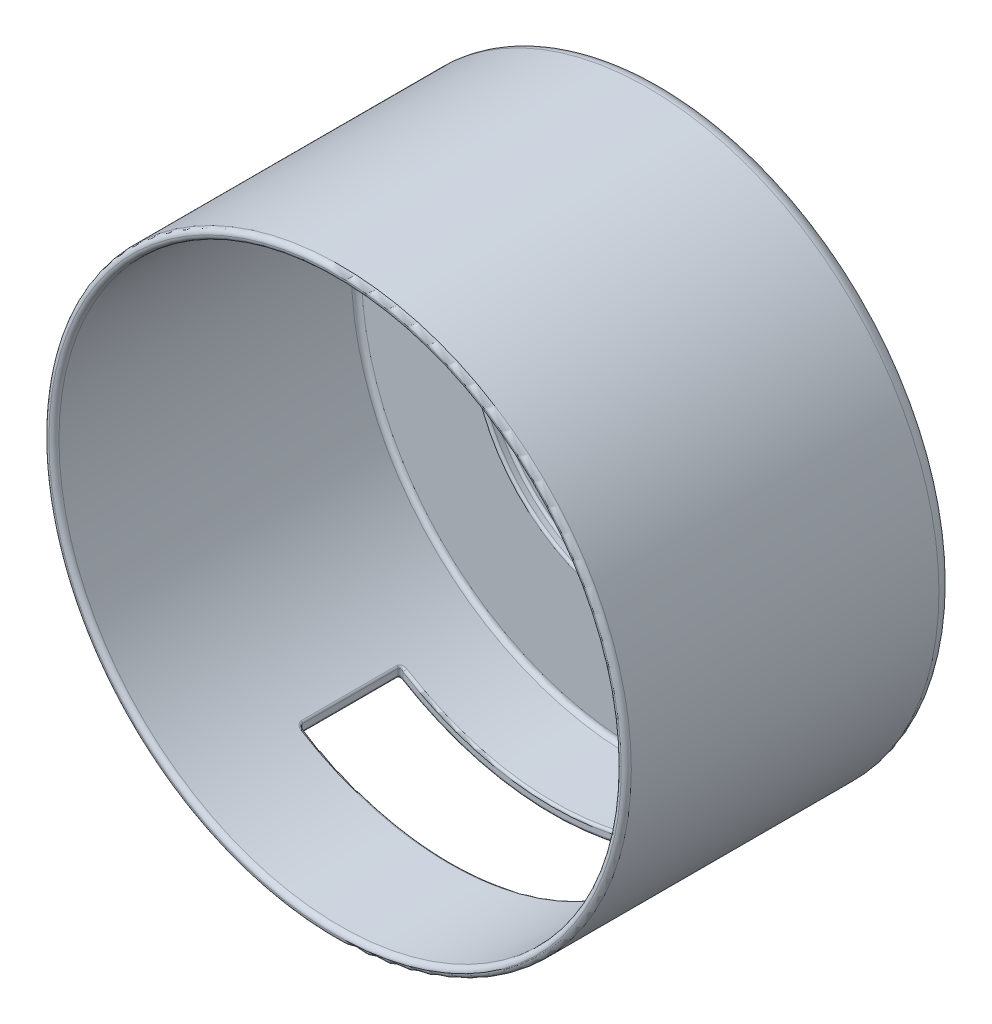
SolidWorks part; units mm, degrees
material "Custom PLA"
ref_plane "Front Plane" through (0, 0, 0) normal (0, 0, 1) x (1, 0, 0)
ref_plane "Top Plane" through (0, 0, 0) normal (0, 1, 0) x (1, 0, 0)
ref_plane "Right Plane" through (0, 0, 0) normal (1, 0, 0) x (0, 0, -1)
sketch "Sketch3" plane through (0, 0, 0) normal (0, 0, 1) x (1, 0, 0)
  circle A0 centre (0, 0) radius 57.75
  dimension "D1" = 115.5
extrude "Boss-Extrude4" add sketch "Sketch3" along normal blind 65
sketch "Sketch4" plane through (0, 0, 65) normal (0, 0, 1) x (1, 0, 0)
  circle A0 centre (0, 0) radius 55.75
  dimension "D1" = 111.5
extrude "Cut-Extrude2" cut sketch "Sketch4" against normal blind 60
sketch "Sketch5" plane through (0, 0, 0) normal (0, 0, -1) x (-1, 0, 0)
  circle A0 centre (0, 0) radius 27.5
  dimension "D1" = 55
extrude "Boss-Extrude6" add sketch "Sketch5" along normal blind 5 contours A0
sketch "Sketch10" plane through (0, 0, -5) normal (0, 0, -1) x (-1, 0, 0)
  circle A0 centre (0, 0) radius 20
  dimension "D1" = 40
extrude "Cut-Extrude5" cut sketch "Sketch10" against normal blind 40
sketch "Sketch11" plane through (0, 0, 5) normal (0, 0, -1) x (-1, 0, 0)
  circle A0 centre (0, 0) radius 23 construction
  circle A1 centre (0, 23) radius 1.55
  dimension "D1" = 46
  dimension "D2" = 3.1
extrude "Cut-Extrude6" cut sketch "Sketch11" along normal up to next
pattern_circular "CirPattern2" count 8 over 360 about axis through (0, 0, -5) along (0, 0, -1) of "Cut-Extrude6"
sketch "Sketch12" plane through (0, 0, 5) normal (0, 0, 1) x (1, 0, 0)
  circle A0 centre (0, 0) radius 32.5
  dimension "D1" = 65
extrude "Cut-Extrude7" cut sketch "Sketch12" against normal blind 2
sketch "Sketch13" plane through (0, 0, 3) normal (0, 0, 1) x (1, 0, 0)
  line L0 (0, 0) -> (0, 32.5) construction
  circle A0 centre (0, 0) radius 22.5 construction
  circle A1 centre (0, 0) radius 32.5 construction
  circle A2 centre (0, 23) radius 2.875
  dimension "D1" = 45
  dimension "D2" = 5.75
extrude "Cut-Extrude8" cut sketch "Sketch13" against normal blind 6
pattern_circular "CirPattern3" count 8 over 360 about axis through (0, 0, 5) along (0, 0, 1) of "Cut-Extrude8"
fillet "Fillet1" radius 1 3 edges at (57.75, 0, 65) (55.75, 0, 65) (55.75, 0, 5)
fillet "Fillet2" radius 3 1 edges at (57.75, 0, 0)
fillet "Fillet3" radius 0.5 2 edges at (32.5, 0, 5) (32.5, 0, 3)
fillet "Fillet4" radius 0.5 2 edges at (20, 0, 3) (-20, 0, -5)
fillet "Fillet5" radius 1 2 edges at (-27.5, 0, 0) (-27.5, 0, -5)
sketch "Sketch14" plane through (0, 0, 5) normal (0, 0, 1) x (1, 0, 0)
  line L0 (0, 62.9632) -> (0, -75.9722) construction
  circle A0 centre (0, 0) radius 42.5 construction
  circle A1 centre (0, 42.5) radius 1.8
  dimension "D1" = 85
  dimension "D2" = 3.6
extrude "Cut-Extrude9" [suppressed] cut sketch "Sketch14" against normal up to next
pattern_circular "CirPattern4" [suppressed] count 8 over 360 of bodies 117
sketch "Sketch15" [suppressed] plane through (0, 0, 0) normal (0, 0, -1) x (-1, 0, 0)
  line L0 (0, 63.4836) -> (0, -76.7527) construction
  circle A0 centre (0, 0) radius 42.5 construction
  circle A1 centre (0, 42.5) radius 3.5
  dimension "D1" = 85
  dimension "D2" = 7
extrude "Cut-Extrude10" [suppressed] cut sketch "Sketch15" against normal blind 2
pattern_circular "CirPattern5" [suppressed] count 8 over 360 of bodies 119
ref_plane "Plane1" through (0, -57.75, 0) normal (0, -1, 0) x (-1, 0, 0)
sketch "Sketch16" plane through (0, -57.75, 0) normal (0, 1, 0) x (1, 0, 0)
  line L0 (0, 13.0017) -> (0, -82.356) construction
  line L1 (56.75, -65) -> (-56.75, -65) construction
  line L2 (-30, -42) -> (30, -42)
  line L3 (-30, -42) -> (-30, -22)
  line L4 (-30, -22) -> (30, -22)
  line L5 (30, -42) -> (30, -22)
  point P9 (0, -42)
  dimension "D1" = 23
  dimension "D2" = 60
  dimension "D3" = 20
extrude "Cut-Extrude11" cut sketch "Sketch16" along normal blind 50
fillet "Fillet6" radius 0.5 12 edges at (0, -55.75, 42) (0, -57.75, 42) (0, -55.75, 22) (0, -57.75, 22) (30, -48.1682, 22) (30, -46.99, 32) (30, -48.1682, 42) (30, -49.3464, 32) (-30, -48.1682, 42) (-30, -46.99, 32) (-30, -48.1682, 22) (-30, -49.3464, 32)
